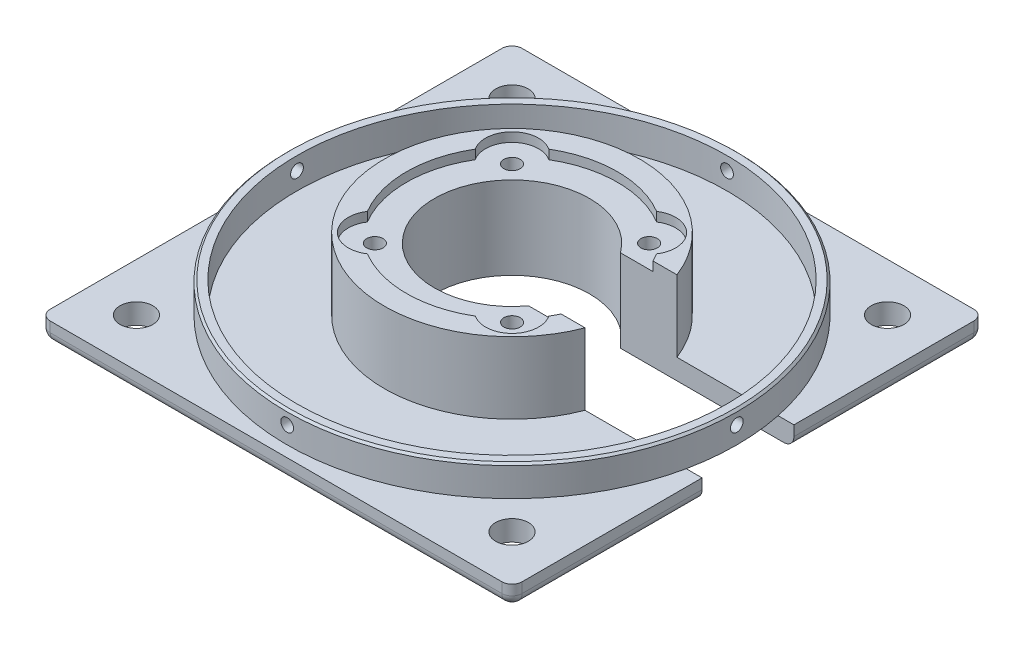
SolidWorks part; units mm, degrees
ref_plane "Front Plane" through (0, 0, 0) normal (0, 0, 1) x (1, 0, 0)
ref_plane "Top Plane" through (0, 0, 0) normal (0, 1, 0) x (1, 0, 0)
ref_plane "Right Plane" through (0, 0, 0) normal (1, 0, 0) x (0, 0, -1)
sketch "Sketch3" plane through (0, 0, 0) normal (0, 1, 0) x (1, 0, 0)
  circle A0 centre (0, 0) radius 7.6
  circle A1 centre (0, 0) radius 12.5
  dimension "D1" = 15.2
  dimension "D2" = 25
extrude "Boss-Extrude2" add sketch "Sketch3" along normal blind 9
sketch "Sketch4" plane through (0, 9, 0) normal (0, 1, 0) x (1, 0, 0)
  line L0 (6.1245, 4.5) -> (6.1245, -4.5)
  line L1 (6.1245, -4.5) -> (13.2817, -4.5)
  line L2 (13.2817, -4.5) -> (13.2817, 4.5)
  line L3 (13.2817, 4.5) -> (6.1245, 4.5)
  circle A0 centre (0, 0) radius 7.6 construction
  point P0 (0, 0)
  point P1 (6.1245, 4.5)
  point P3 (6.1245, -4.5)
  dimension "D1" = 4.5
extrude "Cut-Extrude2" cut sketch "Sketch4" against normal blind 9
sketch "Sketch5" plane through (0, 9, 0) normal (0, 1, 0) x (1, 0, 0)
  line L0 (0, 0) -> (17.4279, 0) construction
  line L1 (0, 0) -> (-11.2462, -11.2462) construction
  line L2 (0, 0) -> (-11.0539, 11.0539) construction
  point P0 (0, 0)
  point P1 (-6.715, 6.72)
  point P3 (-6.715, -6.72)
  point P9 (6.72, -6.715)
  point P10 (6.72, 6.715)
  dimension "D1" = 6.72
  dimension "D2" = 9.5
  dimension "D3" = 6.72
  dimension "D4" = 9.5
sketch "Sketch6" plane through (0, 9, 0) normal (0, 1, 0) x (1, 0, 0)
  line L0 (0, 0) -> (-11.2462, -11.2462) construction
  line L1 (0, 0) -> (-11.0539, 11.0539) construction
  line L2 (0, 0) -> (17.4279, 0) construction
  point P0 (5.2883, -8.8853)
  point P9 (-8.8853, 5.2883)
  point P12 (5.2883, 8.8853)
  point P14 (8.8893, -5.2817)
  point P15 (-5.2817, 8.8893)
  point P16 (8.8893, 5.2817)
  point P17 (-5.2817, -8.8893)
  point P18 (-8.8853, -5.2883)
  dimension "D1" = 2.6
  dimension "D2" = 10.34
  dimension "D3" = 2.6
  dimension "D4" = 10.34
sketch "Sketch8" plane through (0, 9, 0) normal (0, 1, 0) x (1, 0, 0)
  circle A0 centre (0, 0) radius 10.34
extrude "Cut-Extrude5" cut sketch "Sketch8" against normal blind 0.9
hole_wizard "Tap Drill for M2x0.4 Tap1" positions "3DSketch1" profile "Sketch10" hole size "M2x0.4" standard "ANSI Metric" end condition through all
sketch3d "3DSketch1"
  point P0 (6.72, 9, 6.715)
  point P3 (-6.715, 9, 6.72)
  point P6 (-6.715, 9, -6.72)
  point P9 (6.72, 9, -6.715)
sketch "Sketch10" plane through (6.72, 9, 6.715) normal (1, 0, 0) x (0, 0, 1)
  line L0 (0, 0) -> (0, 9)
  line L1 (0, 9) -> (0.8, 9)
  line L2 (0.8, 9) -> (0.8, 0)
  line L5 (0.8, 0) -> (0, 0)
  line L11 (0, -6.35) -> (0, 107.95) construction
  dimension "Thru Hole Dia." = 1.6
  dimension "Thru Hole Depth" = 9
sketch "Sketch11" plane through (0, 9, 0) normal (0, 1, 0) x (1, 0, 0)
  line L0 (8.8893, 5.2817) -> (5.2883, 8.8853)
  line L1 (8.8893, -5.2817) -> (5.2883, -8.8853)
  line L2 (-5.2817, -8.8893) -> (-8.8853, -5.2883)
  line L3 (-5.2817, 8.8893) -> (-8.8853, 5.2883)
  arc A0 (5.2883, -8.8853) -> (8.8893, -5.2817) centre (6.72, -6.715) ccw
  arc A1 (9.3094, 4.5) -> (9.3094, -4.5) centre (0, 0) ccw construction
  arc A2 (8.8893, 5.2817) -> (5.2883, 8.8853) centre (6.72, 6.715) ccw
  arc A3 (-5.2817, 8.8893) -> (-8.8853, 5.2883) centre (-6.715, 6.72) ccw
  arc A4 (-8.8853, -5.2883) -> (-5.2817, -8.8893) centre (-6.715, -6.72) ccw
extrude "Cut-Extrude6" cut sketch "Sketch11" against normal blind 0.9
sketch "Sketch12" plane through (0, 0, 0) normal (0, -1, 0) x (1, 0, 0)
  line L0 (0, 0) -> (17.7684, 0) construction
  line L1 (0, 0) -> (0, 18.0241) construction
  line L2 (23.125, -23.125) -> (-23.125, -23.125)
  line L3 (-23.125, -23.125) -> (-23.125, 23.125)
  line L4 (-23.125, 23.125) -> (23.125, 23.125)
  line L9 (6.4622, 4) -> (23.125, 4)
  line L11 (23.125, -4.5) -> (6.1245, -4.5)
  line L13 (23.125, -23.125) -> (23.125, -4.5)
  line L14 (23.125, 23.125) -> (23.125, 4)
  arc A0 (6.1245, -4.5) -> (6.4622, 4) centre (0, 0) cw
  circle A1 centre (0, 0) radius 7.6 construction
  point P0 (23.125, -23.125)
  point P4 (23.125, 23.125)
  point P5 (-23.125, 23.125)
  point P7 (-23.125, -23.125)
  dimension "D1" = 23.125
  dimension "D2" = 23.125
extrude "Boss-Extrude4" add sketch "Sketch12" against normal blind 2
fillet "Fillet2" radius 1 2 edges at (-23.125, 0, 0) (0, 0, 23.125)
fillet "Fillet3" radius 1 2 edges at (-22.8321, 0.2929, 22.8321) (-23.125, 1.5, 23.125)
sketch "Sketch13" plane through (0, 0, 0) normal (0, -1, 0) x (1, 0, 0)
  line L0 (0, 0) -> (-25.0462, 0) construction
  line L1 (0, 0) -> (0, 26.5218) construction
  point P0 (18.3989, -18.3989)
  point P5 (18.3989, 18.3989)
  point P6 (-18.3989, -18.3989)
  point P7 (-18.3989, 18.3989)
  dimension "D1" = 18.3989
  dimension "D2" = 18.3989
hole_wizard "M3 Clearance Hole1" positions "3DSketch2" profile "Sketch14" hole size "M3" standard "ANSI Metric" end condition through all
sketch3d "3DSketch2"
  point P0 (18.3989, 0, 18.3989)
  point P3 (18.3989, 0, -18.3989)
  point P6 (-18.3989, 0, -18.3989)
  point P9 (-18.3989, 0, 18.3989)
sketch "Sketch14" plane through (18.3989, 0, 18.3989) normal (1, 0, 0) x (0, 0, -1)
  line L0 (0, 0) -> (0, 9)
  line L1 (0, 9) -> (1.6, 9)
  line L2 (1.6, 9) -> (1.6, 0)
  line L5 (1.6, 0) -> (0, 0)
  line L11 (0, -6.35) -> (0, 107.95) construction
  dimension "Thru Hole Dia." = 3.2
  dimension "Thru Hole Depth" = 9
fillet "Fillet4" radius 1 7 edges at (23.125, 1.5, 23.125) (23.125, 0.2929, 22.8321) (-23.125, 1.5, -23.125) (-22.8321, 0.2929, -23.125) (23.125, 0, 13.0625) (23.125, 0, -13.8125) (0.5, 0, -23.125)
fillet "Fillet5" radius 1 2 edges at (22.8321, 0.2929, -22.8321) (23.125, 1.5, -23.125)
sketch "Sketch15" plane through (0, 2, 0) normal (0, 1, 0) x (1, 0, 0)
  circle A0 centre (0, 0) radius 22.0375
  circle A1 centre (0, 0) radius 21.075
  point P0 (0, 0)
extrude "Boss-Extrude6" add sketch "Sketch15" along normal blind 3
hole_wizard "Tap Drill for M1.6x0.35 Tap1" positions "3DSketch4" profile "Sketch25" hole size "M1.6x0.35" standard "ANSI Metric" end condition up to next
sketch3d "3DSketch4"
  point P0 (22.0375, 3.7, 0)
sketch "Sketch25" plane through (22.0375, 3.7, 0) normal (0, 1, 0) x (0, 0, -1)
  line L0 (0, 0) -> (0, 0.9625)
  line L1 (0, 0.9625) -> (0.625, 0.9625)
  line L2 (0.625, 0.9625) -> (0.625, 0)
  line L5 (0.625, 0) -> (0, 0)
  line L11 (0, -6.35) -> (0, 107.95) construction
  dimension "Thru Hole Dia." = 1.25
  dimension "Thru Hole Depth" = 0.9625
ref_axis "Axis1" through (0, 8.1, 0) along (0, -1, 0)
pattern_circular "CirPattern1" count 4 over 360 about axis through (0, 8.1, 0) along (0, -1, 0) of "Tap Drill for M1.6x0.35 Tap1"
chamfer "Chamfer1" distance 0.2 angle 45 1 edges at (0, 5, 22.0375)
sketch "Sketch26" plane through (0, 2, 0) normal (0, 1, 0) x (1, 0, 0)
  line L1 (6.1245, -4.5) -> (23.125, -4.5)
  line L2 (6.1245, -4.5) -> (6.1245, 4.5)
  line L3 (6.1245, 4.5) -> (23.125, 4.5)
  line L4 (23.125, -4.5) -> (23.125, 4.5)
extrude "Cut-Extrude7" cut sketch "Sketch26" against normal up to next
